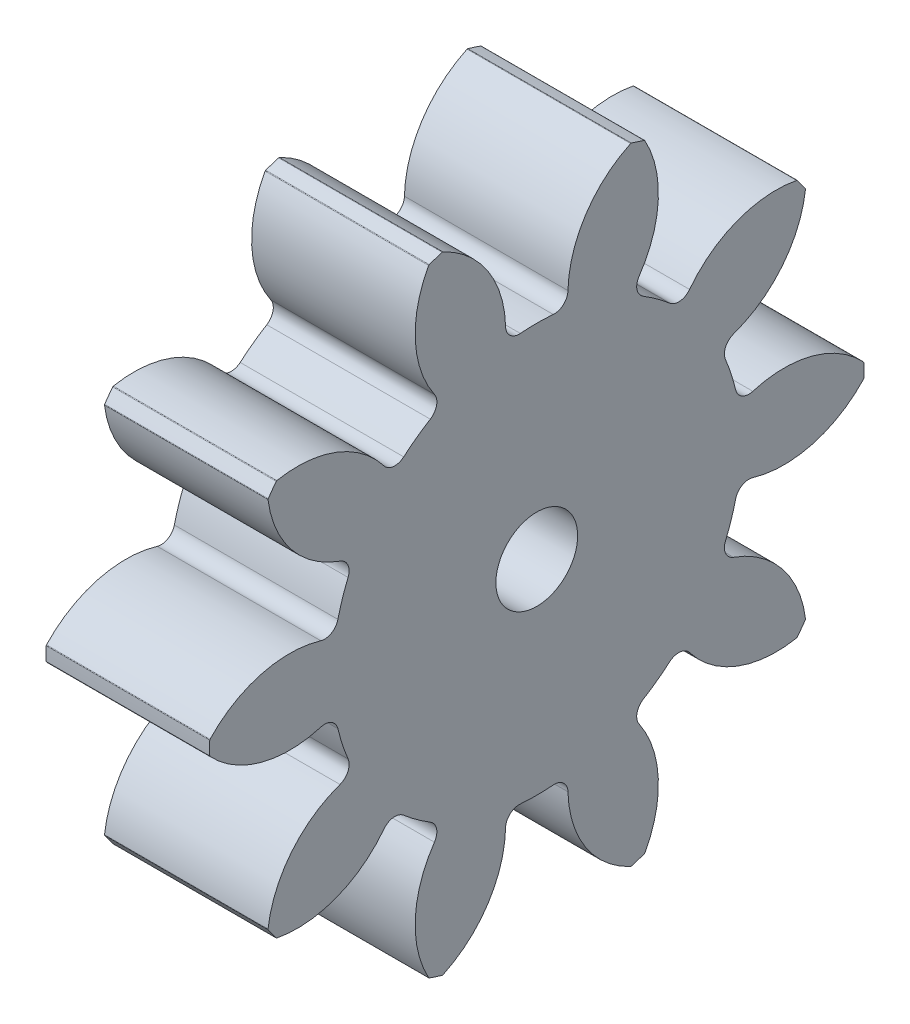
SolidWorks part; units mm, degrees
ref_plane "Plane1" through (0, 0, 0) normal (0, 0, 1) x (1, 0, 0)
ref_plane "Plane2" through (0, 0, 0) normal (0, 1, 0) x (1, 0, 0)
ref_plane "Plane3" through (0, 0, 0) normal (1, 0, 0) x (0, 0, -1)
sketch "HoldingSke" plane through (0, 0, 0) normal (0, 1, 0) x (1, 0, 0)
  line L0 (0, 0) -> (0.2462, -0.0434)
  line L1 (-15, 0) -> (100, 0) construction
  line L2 (0, 0) -> (-2.1039, 2.3779)
  line L3 (0, 0) -> (-11.863, 4.5341)
  line L4 (0, 0) -> (8.5048, 1.4996)
  line L5 (0, 0) -> (-46.8476, -17.4728)
  line L6 (0, 0) -> (-9.9476, -6.7116)
  line L7 (-2.1039, 2.3779) -> (8.6586, 51.2059)
  line L8 (-76.2, 54.61) -> (-75.2, 54.61)
  line L9 (-71.009, 38.7566) -> (-53.1078, 45.2721)
  line L10 (-76.2, 71.12) -> (104.1128, 71.12)
  line L11 (0, 0) -> (-12, 0)
  line L12 (-76.2, 101.6) -> (-76.073, 101.6)
  line L13 (24.9733, 27.94) -> (52.9518, 28.4284)
  line L14 (24.9733, 27.94) -> (24.9743, 27.94)
  line L15 (24.9733, 27.94) -> (100.4006, 29.5858)
  line L16 (-63.627, -4) -> (-12.827, -4)
  circle A0 centre (0, 0) radius 3
  circle A1 centre (0, 0) radius 14.999
  circle A2 centre (0, 0) radius 37.5
  circle A3 centre (0, 0) radius 3
  dimension "MHD" = 29.998
  dimension "Hub_dia" = 75
  dimension "Bore" = 6
  dimension "MBD" = 6
  dimension "Num_teeth" = 10
  dimension "Pitch_radius" = 180.3128
  dimension "Pitch" = 0.25
  dimension "Width" = 12
  dimension "Overall_len" = 50
  dimension "Show_teeth" = 10
  dimension "Thickness" = 12
  dimension "OAL" = 50.0001
  dimension "T_dim" = 1
  dimension "Ap" = 20
  dimension "H" = 19.05
  dimension "Backlash" = 0.127
  dimension "Addendum_fac" = 1
  dimension "Dedendum_fac" = 1.25
  dimension "Clearance_fac" = 0.25
  dimension "Dedendum_add" = 0.001
  dimension "Module" = 4
sketch "BasProSke" plane through (0, 0, 0) normal (0, 1, 0) x (1, 0, 0)
  line L0 (-10, 0) -> (60, 0) construction
  line L1 (0, 0) -> (0, 24)
  line L2 (0, 0) -> (12, 0)
  line L3 (12, 0) -> (12, 24)
  line L4 (12, 24) -> (0, 24)
  dimension "Diameter" = 48
  dimension "Thickness" = 12
revolve "Base-Revolve" add sketch "BasProSke" angle 360 about L0
sketch "TooCutSke" plane through (0, 0, 0) normal (1, 0, 0) x (0, 0, -1)
  line L1 (0, 0) -> (0, 107) construction
  line L2 (0, 0) -> (-3.3505, 19.7173) construction
  line L3 (0, 0) -> (-12.2295, 37.6384) construction
  line L4 (-3.3505, 19.7173) -> (-6.1147, 18.8192) construction
  arc A0 (2.338, 14.8157) -> (-2.338, 14.8157) centre (0, 0) ccw
  arc A1 (6.9466, 22.9992) -> (-6.9466, 22.9992) centre (0, 0) ccw
  circle A2 centre (0, 0) radius 20 construction
  circle A3 centre (0, 0) radius 18.7939 construction
  arc A4 (-2.338, 14.8157) -> (-6.9466, 22.9992) centre (-10.2857, 15.7294) ccw
  arc A5 (6.9466, 22.9992) -> (2.338, 14.8157) centre (10.2857, 15.7294) ccw
  dimension "Root_dia" = 29.998
  dimension "Overcut_dia" = 48.0508
  dimension "Pitch_dia" = 40
  dimension "Base_dia" = 37.5877
  dimension "Flank_rad" = 8
  dimension "Half_ang" = 18
  dimension "Half_CT" = 2.9064
extrude "ToothCut" cut sketch "TooCutSke" along normal through all
fillet "Breaks" radius 0.08 2 edges at (6, 22.9832, -6.9119) (6, 22.9832, 6.9119) tangent propagation no
fillet "RootFillets" radius 1.001 2 edges at (6, 14.8157, -2.338) (6, 14.8157, 2.338)
pattern_circular "TeethCuts" count 10 every 36 about axis through (-10, 0, 0) along (1, 0, 0) of "ToothCut", "RootFillets", "Breaks"
sketch "HubNeaOneSke" plane through (0, 0, 0) normal (-1, 0, 0) x (0, 0, 1)
  circle A0 centre (0, 0) radius 14.999
  dimension "Diameter" = 29.998
extrude "HubNearOne" [suppressed] add sketch "HubNeaOneSke" along normal blind 38.0001
sketch "HubNeaBotSke" plane through (0, 0, 0) normal (-1, 0, 0) x (0, 0, 1)
  circle A0 centre (0, 0) radius 14.999
  dimension "Diameter" = 29.998
extrude "HubNearBoth" [suppressed] add sketch "HubNeaBotSke" along normal blind 19
ref_plane "FarPln" through (12, 0, 0) normal (1, 0, 0) x (0, 0, -1)
sketch "HubFarSke" plane through (12, 0, 0) normal (1, 0, 0) x (0, 0, -1)
  circle A0 centre (0, 0) radius 14.999
  dimension "Diameter" = 29.998
extrude "HubFar" [suppressed] add sketch "HubFarSke" along normal blind 19
sketch "BorSke" plane through (0, 0, 0) normal (1, 0, 0) x (0, 0, -1)
  circle A0 centre (0, 0) radius 3
  dimension "Diameter" = 6
extrude "Bore" cut sketch "BorSke" along normal mid plane 100.0001
sketch "KeySke" plane through (0, 0, 0) normal (1, 0, 0) x (0, 0, -1)
  line L0 (-1, 0) -> (-1, 4)
  line L1 (-1, 4) -> (1, 4)
  line L2 (1, 4) -> (1, 0)
  line L3 (0, 0) -> (0, 34) construction
  line L4 (-1, 0) -> (1, 0)
  dimension "Offset" = 4
  dimension "Width" = 2
extrude "Keyway" [suppressed] cut sketch "KeySke" along normal mid plane 100.0001
pattern_circular "Keyway2" [suppressed] count 2 every 90 about axis through (-10, 0, 0) along (1, 0, 0)
sketch "Sketch1" plane through (0, 0, 0) normal (-1, 0, 0) x (0, 0, 1)
  point P0 (0, 0)
sketch "Sketch2" plane through (0, 0, 0) normal (-1, 0, 0) x (0, 0, 1)
  arc A0 (9.7639, 11.3858) -> (7.8113, 12.8044) centre (0, 0) ccw construction
  point P5 (8.8162, 12.1344)
ref_axis "Axis1" through (0, 0, 0) along (0, 0.809, 0.5878)
equation "' \"Module@HoldingSke\" = 6.35"
equation "' \"Num_teeth@HoldingSke\" = 12"
equation "' \"Ap@HoldingSke\" =  20"
equation "' \"Width@HoldingSke\" = 0.5 * 25.4"
equation "' \"Hub_dia@HoldingSke\"= 1 * 25.4"
equation "' \"Overall_len@HoldingSke\" = 1.0 * 25.4"
equation "' \"Bore@HoldingSke\" = 0.75 * 25.4"
equation "' \"T_dim@HoldingSke\" = 0.1 * 25.4"
equation "' \"Width@KeySke\" = 0.25 * 25.4"
equation "' \"Show_teeth@HoldingSke\" = 13"
equation "' \"Backlash@HoldingSke\" = 0.009 * 25.4"
equation "' \"Addendum_fac@HoldingSke\" = 1.0"
equation "' \"Dedendum_fac@HoldingSke\" = 1.25"
equation "' \"Dedendum_add@HoldingSke\" = 0.00005 * 25.4"
equation "' \"Clearance_fac@HoldingSke\" = 0.25"
equation "\"Pitch@HoldingSke\" = 1 / \"Module@HoldingSke\""
equation "\"Overcut_dia@TooCutSke\" = (\"Num_teeth@HoldingSke\" + 2 * \"Addendum_fac@HoldingSke\") / \"Pitch@HoldingSke\" + 0.002 * 25.4"
equation "\"Pitch_dia@TooCutSke\" = \"Num_teeth@HoldingSke\" / \"Pitch@HoldingSke\""
equation "\"Base_dia@TooCutSke\" = \"Num_teeth@HoldingSke\" / \"Pitch@HoldingSke\" * cos((\"Ap@HoldingSke\"  * 3.14159265 / 180))"
equation "\"Root_dia@TooCutSke\" = (\"Num_teeth@HoldingSke\" + 2) / \"Pitch@HoldingSke\" - 2 * (\"Addendum_fac@HoldingSke\" + \"Dedendum_fac@HoldingSke\") / \"Pitch@HoldingSke\" - \"Dedendum_add@HoldingSke\" * 2"
equation "\"Half_ang@TooCutSke\" = 180 / \"Num_teeth@HoldingSke\""
equation "\"Half_CT@TooCutSke\" = \"Num_teeth@HoldingSke\" / \"Pitch@HoldingSke\" * sin((3.14159265 / 2 / \"Num_teeth@HoldingSke\")) / 2 - 7 * \"Backlash@HoldingSke\" / 4"
equation "\"Flank_rad@TooCutSke\" = \"Num_teeth@HoldingSke\" / \"Pitch@HoldingSke\" / 5"
equation "\"Radius@RootFillets\" = \"Clearance_fac@HoldingSke\" / \"Pitch@HoldingSke\" + \"Dedendum_add@HoldingSke\""
equation "\"Break_rad@Breaks\" = 0.02 / \"Pitch@HoldingSke\""
equation "\"Thickness@HoldingSke\" = \"Width@HoldingSke\""
equation "\"OAL@HoldingSke\" = \"Thickness@HoldingSke\""
equation "\"MHD@HoldingSke\" = (\"Num_teeth@HoldingSke\" + 2) / \"Pitch@HoldingSke\" - 2 * (\"Addendum_fac@HoldingSke\" + \"Dedendum_fac@HoldingSke\")  / \"Pitch@HoldingSke\" - \"Dedendum_add@HoldingSke\" * 2"
equation "\"MBD@HoldingSke\" = (\"Num_teeth@HoldingSke\" + 2) / \"Pitch@HoldingSke\" - 2 * (\"Addendum_fac@HoldingSke\" + \"Dedendum_fac@HoldingSke\")  / \"Pitch@HoldingSke\" - \"Dedendum_add@HoldingSke\" * 2 - 0.002 * 25.4"
equation "\"MHD@HoldingSke\" = ((sgn( \"MHD@HoldingSke\" - \"Hub_dia@HoldingSke\" )-1)*( \"MHD@HoldingSke\" - \"Hub_dia@HoldingSke\" ))/-2+ \"Hub_dia@HoldingSke\""
equation "\"MBD@HoldingSke\" = ((sgn( \"MBD@HoldingSke\" - \"Bore@HoldingSke\" )-1)*( \"MBD@HoldingSke\" - \"Bore@HoldingSke\" ))/-2+ \"Bore@HoldingSke\""
equation "\"OAL@HoldingSke\" = ((sgn( \"OAL@HoldingSke\" - \"Overall_len@HoldingSke\" )+1)*( \"OAL@HoldingSke\" - \"Overall_len@HoldingSke\" ))/2 + \"Overall_len@HoldingSke\" + 0.000002 * 25.4"
equation "\"Num_teeth@TeethCuts\" = int( \"Show_teeth@HoldingSke\" ) + 1"
equation "\"Num_teeth@TeethCuts\" = ((sgn( \"Num_teeth@TeethCuts\" - \"Num_teeth@HoldingSke\" )-1)*( \"Num_teeth@TeethCuts\" - \"Num_teeth@HoldingSke\" ))/-2+ \"Num_teeth@HoldingSke\""
equation "\"Num_teeth@TeethCuts\" = ((sgn( \"Num_teeth@TeethCuts\" - 2.0)+1)*( \"Num_teeth@TeethCuts\" - 2.0))/2 +2.0"
equation "\"Angle@TeethCuts\" = 360.0 / \"Num_teeth@HoldingSke\""
equation "\"Diameter@BasProSke\" = (\"Num_teeth@HoldingSke\" + 2 * \"Addendum_fac@HoldingSke\") / \"Pitch@HoldingSke\""
equation "\"Thickness@BasProSke\"  = \"Thickness@HoldingSke\""
equation "' \"Fillet_rad@BasProSke\" =  \"Thickness@HoldingSke\" * 0.05"
equation "\"MHD@HoldingSke\" = ((sgn( \"MHD@HoldingSke\" - \"Root_dia@TooCutSke\" )-1)*( \"MHD@HoldingSke\" - \"Root_dia@TooCutSke\" ))/-2+ \"Root_dia@TooCutSke\""
equation "\"Diameter@HubNeaOneSke\" = \"MHD@HoldingSke\""
equation "\"Length@HubNearOne\" = \"OAL@HoldingSke\" - \"Thickness@BasProSke\""
equation "\"Diameter@HubNeaBotSke\" = \"MHD@HoldingSke\""
equation "\"Length@HubNearBoth\" = ( \"OAL@HoldingSke\" - \"Thickness@BasProSke\" ) / 2.0"
equation "\"Thickness@FarPln\" = \"Thickness@BasProSke\""
equation "\"Diameter@HubFarSke\" = \"MHD@HoldingSke\""
equation "\"Length@HubFar\" = ( \"OAL@HoldingSke\" - \"Thickness@BasProSke\" ) / 2.0"
equation "\"Diameter@BorSke\" = \"MBD@HoldingSke\""
equation "\"D1@Bore\" = \"OAL@HoldingSke\" * 2.0"
equation "\"D1@Keyway\" = \"OAL@HoldingSke\" * 2.0"
equation "\"Offset@KeySke\" = \"T_dim@HoldingSke\" + \"MBD@HoldingSke\" / 2.0"
